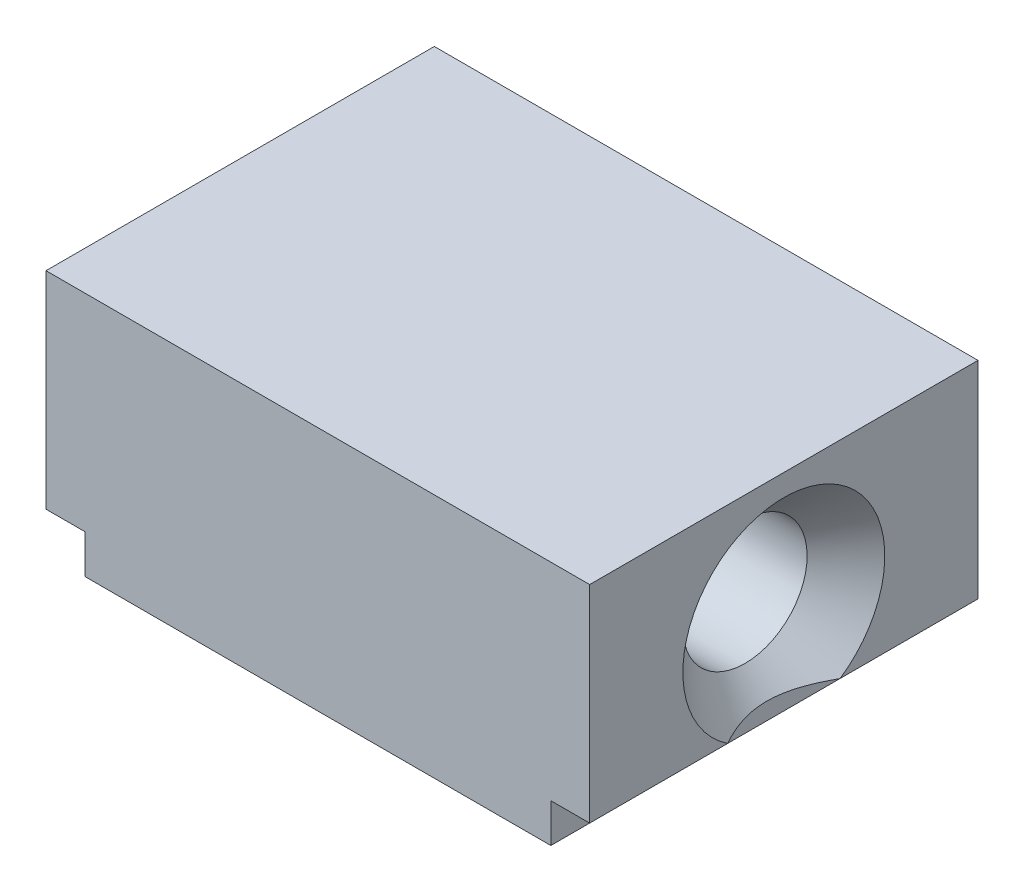
SolidWorks part; units mm, degrees
ref_plane "Front Plane" through (0, 0, 0) normal (0, 0, 1) x (1, 0, 0)
ref_plane "Top Plane" through (0, 0, 0) normal (0, 1, 0) x (1, 0, 0)
ref_plane "Right Plane" through (0, 0, 0) normal (1, 0, 0) x (0, 0, -1)
sketch "Sketch1" plane through (0, 0, 0) normal (0, 1, 0) x (1, 0, 0)
  line L1 (-3, 2.5) -> (3, 2.5)
  line L2 (-3, 2.5) -> (-3, -2.5)
  line L3 (-3, -2.5) -> (3, -2.5)
  line L4 (3, 2.5) -> (3, -2.5)
  line L5 (-3, 2.5) -> (3, -2.5) construction
  line L6 (-3, -2.5) -> (3, 2.5) construction
  point P0 (0, 0)
  dimension "D1" = 6
  dimension "D2" = 5
extrude "Boss-Extrude1" add sketch "Sketch1" along normal blind 0.5
sketch "Sketch2" plane through (0, 0.5, 0) normal (0, 1, 0) x (1, 0, 0)
  line L1 (-3.5, -2.5) -> (3.5, -2.5)
  line L2 (-3.5, -2.5) -> (-3.5, 2.5)
  line L3 (-3.5, 2.5) -> (3.5, 2.5)
  line L4 (3.5, -2.5) -> (3.5, 2.5)
  line L5 (-3.5, -2.5) -> (3.5, 2.5) construction
  line L6 (-3.5, 2.5) -> (3.5, -2.5) construction
  point P0 (0, 0)
  dimension "D1" = 5
  dimension "D2" = 7
extrude "Boss-Extrude2" add sketch "Sketch2" along normal offset from surface (2.66 mm away) 3.16 up to face at (0, 0, 0)
sketch "Sketch3" plane through (-3.5, 0, 0) normal (-1, 0, 0) x (0, 0, 1)
  line L0 (0, 0) -> (0, 3.16) construction
  line L1 (-2.5, 3.16) -> (2.5, 3.16) construction
  circle A0 centre (0, 1.58) radius 0.8
  dimension "D2" = 1.6
  dimension "D1" = 1.58
extrude "Cut-Extrude1" cut sketch "Sketch3" against normal through all
chamfer "Chamfer1" distance 0.5 angle 45 2 edges at (3.5, 1.58, 0.8) (-3.5, 1.58, 0.8)
